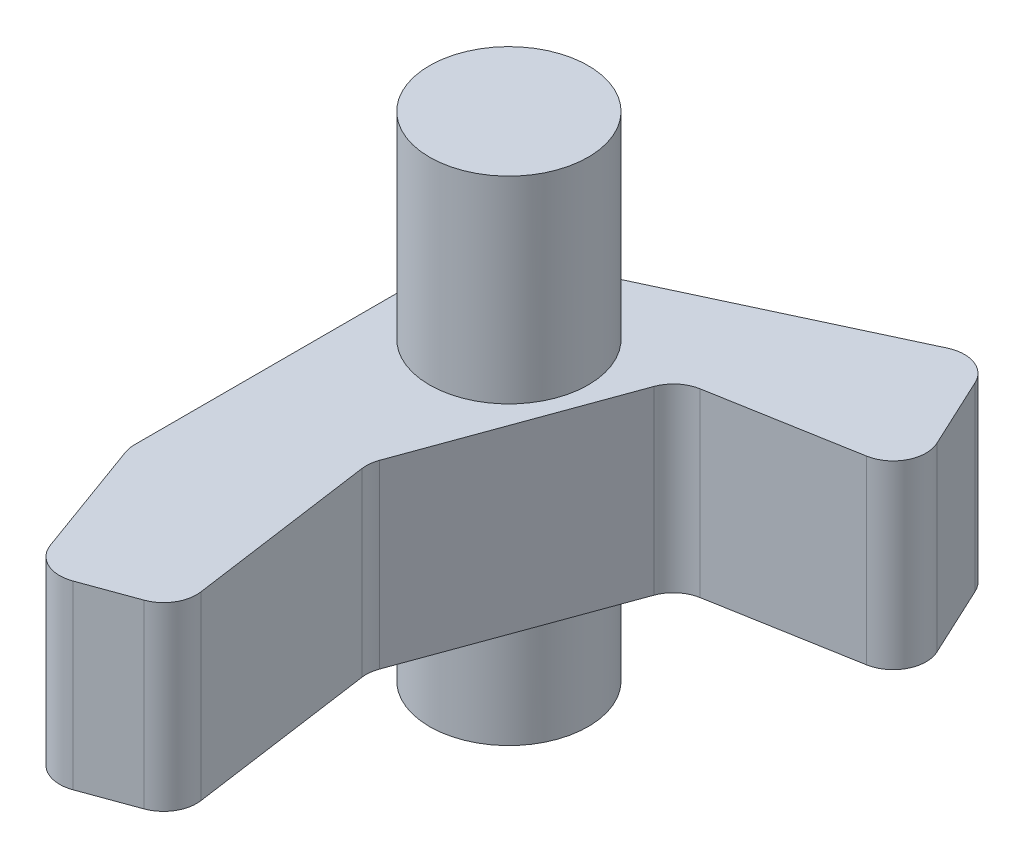
SolidWorks part; units mm, degrees
ref_plane "Front Plane" through (0, 0, 0) normal (0, 0, 1) x (1, 0, 0)
ref_plane "Top Plane" through (0, 0, 0) normal (0, 1, 0) x (1, 0, 0)
ref_plane "Right Plane" through (0, 0, 0) normal (1, 0, 0) x (0, 0, -1)
sketch "Sketch1" plane through (0, 0, 0) normal (0, 1, 0) x (1, 0, 0)
  line L1 (5.0861, 0.2921) -> (4.2895, 2.0002)
  line L2 (4.2895, 2.0002) -> (0, 0)
  line L3 (0, 0) -> (0, -4.2)
  line L10 (5.0861, 0.2921) -> (2.624, -0.142)
  line L11 (2.624, -0.142) -> (1.6377, -2.852)
  line L12 (1.6377, -2.852) -> (2.5634, -5.3953)
  line L13 (0, -4.2) -> (0.684, -6.0794)
  line L14 (2.5634, -5.3953) -> (0.684, -6.0794)
  dimension "D1" = 120
  dimension "D2" = 115
  dimension "D3" = 0.7965
  dimension "D4" = 90
  dimension "D5" = 75
  dimension "D6" = 160
  dimension "D7" = 2.5
  dimension "D8" = 2
  dimension "D9" = 4.2
  dimension "D10" = 90
  dimension "D11" = 2
extrude "Boss-Extrude3" add sketch "Sketch1" along normal blind 2.2
sketch "Sketch2" plane through (0, 0, 0) normal (0, 1, 0) x (1, 0, 0)
  line L0 (4.2895, 2.0002) -> (0, 0) construction
  line L1 (0, 0) -> (0, -4.2) construction
  line L2 (1.6377, -2.852) -> (2.624, -0.142) construction
  circle A0 centre (1.1654, -0.7424) radius 1.1654 construction
  circle A1 centre (1.1654, -0.7424) radius 0.9654
  dimension "D1" = 0.2
chamfer "Chamfer2" distance 0.6 angle 78 1 edges at (2.5634, 1.1, 5.3953) first distance on face at (1.6237, 1.1, 5.7374)
fillet "Fillet1" radius 0.4 7 edges at (0.684, 1.1, 6.0794) (0, 1.1, 4.2) (2.624, 1.1, 0.142) (5.0861, 1.1, -0.2921) (4.2895, 1.1, -2.0002) (1.9996, 1.1, 5.6006) (1.6201, 1.1, 2.9003)
extrude "Boss-Extrude4" add sketch "Sketch2" along normal blind 4.6 and the other way blind 1.4
fillet "Fillet2" radius 1.2 1 edges at (0, 1.1, 0)
